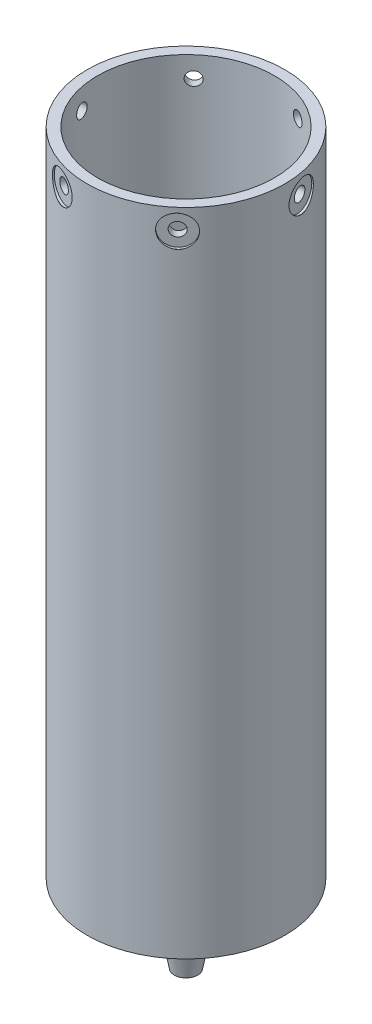
SolidWorks part; units mm, degrees
ref_plane "前视基准面" through (0, 0, 0) normal (0, 0, 1) x (1, 0, 0)
ref_plane "上视基准面" through (0, 0, 0) normal (0, 1, 0) x (1, 0, 0)
ref_plane "右视基准面" through (0, 0, 0) normal (1, 0, 0) x (0, 0, -1)
sketch "草图1" plane through (0, 0, 0) normal (0, 1, 0) x (1, 0, 0)
  circle A0 centre (0, 0) radius 19
  dimension "D1" = 38
extrude "凸台-拉伸1" add sketch "草图1" along normal blind 125
sketch "草图2" plane through (0, 125, 0) normal (0, 1, 0) x (1, 0, 0)
  circle A0 centre (0, 0) radius 17
  dimension "D1" = 34
extrude "切除-拉伸1" cut sketch "草图2" against normal blind 124
sketch "草图3" plane through (0, 0, 0) normal (1, 0, 0) x (0, 0, -1)
  line L0 (0, 0) -> (0, -16.4268) construction
  line L1 (5, 0) -> (2.25, -15)
  line L2 (-19, 0) -> (19, 0) construction
  line L3 (5, 0) -> (0, 0)
  line L4 (2.25, -15) -> (0, -15)
  line L5 (0, 0) -> (0, -15)
  dimension "D1" = 5
  dimension "D2" = 2.25
  dimension "D3" = 15
revolve "旋转1" add sketch "草图3" angle 360 about L0
sketch "草图4" plane through (0, -15, 0) normal (0, -1, 0) x (1, 0, 0)
  circle A0 centre (0, 0) radius 1.875
  dimension "D1" = 3.75
extrude "切除-拉伸2" cut sketch "草图4" against normal blind 124
ref_plane "基准面2" through (0, 121, 0) normal (0, 1, 0) x (1, 0, 0)
hole_wizard "M2 六角头螺栓的柱形沉头孔2" positions "3D草图2" profile "草图11" counterbore size "M2" standard "GB" end condition up to next
sketch3d "3D草图2"
  point P1 (-18.6191, 121.0149, 3.7852)
  point P5 (-4.3131, 161.2634, 0)
  point P11 (0, 0, 0)
sketch "草图11" plane through (-18.6191, 121.0149, 3.7852) normal (0, 1, 0) x (0.1992, 0, 0.98)
  line L0 (0, 0) -> (0, 2)
  line L1 (0, 2) -> (1.3, 2)
  line L3 (1.3, 2) -> (1.3, 0.5)
  line L4 (3, 0.5) -> (1.3, 0.5)
  line L5 (3, 0.5) -> (3, 0.025)
  line L6 (3, 0.025) -> (3.025, 0)
  line L7 (3.025, 0) -> (0, 0)
  line L8 (-3, 0.025) -> (-3.025, 0) construction
  line L11 (0, -6.35) -> (0, 107.95) construction
  dimension "通孔孔直径" = 2.6
  dimension "通孔孔深度" = 2
  dimension "柱形沉头孔直径" = 6
  dimension "柱形沉头孔深度" = 0.5
  dimension "近端锥形沉头孔直径" = 6.05
  dimension "近端锥形沉头孔角度" = 90
sketch "草图12" plane through (0, 0, 0) normal (1, 0, 0) x (0, 0, -1)
  line L0 (0, -22.0197) -> (0, 127.6075) construction
pattern_circular "阵列(圆周)2" count 6 over 360 about axis through (0, -22.0197, 0) along (0, 1, 0) of "M2 六角头螺栓的柱形沉头孔2" reverse direction yes
